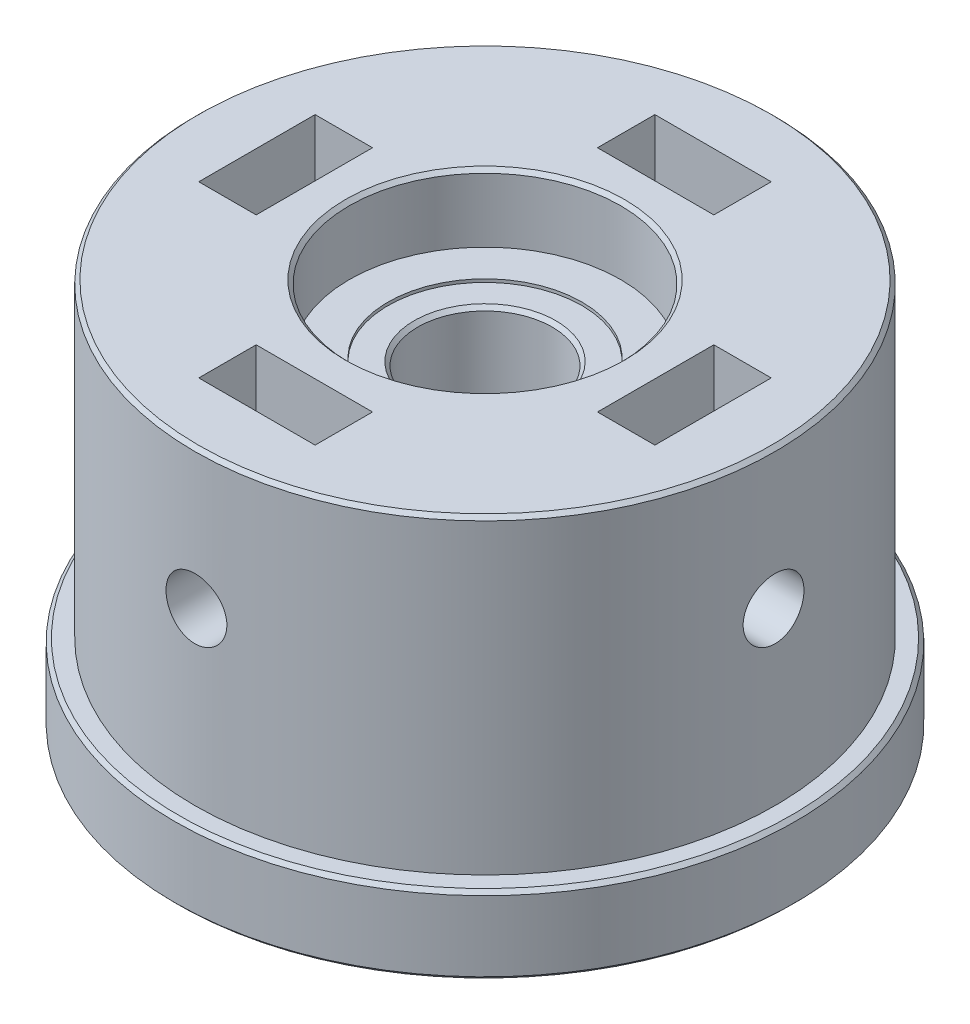
SolidWorks part; units mm, degrees
material "Nylon 101"
ref_plane "Front Plane" through (0, 0, 0) normal (0, 0, 1) x (1, 0, 0)
ref_plane "Top Plane" through (0, 0, 0) normal (0, 1, 0) x (1, 0, 0)
ref_plane "Right Plane" through (0, 0, 0) normal (1, 0, 0) x (0, 0, -1)
sketch "Sketch1" plane through (0, 0, 0) normal (0, 1, 0) x (1, 0, 0)
  circle A0 centre (0, 0) radius 23.749
  dimension "D1" = 47.498
extrude "Boss-Extrude1" add sketch "Sketch1" along normal blind 25.4
sketch "Sketch2" plane through (0, 0, 0) normal (0, -1, 0) x (1, 0, 0)
  circle A0 centre (0, 0) radius 25.4
  dimension "D1" = 50.8
extrude "Boss-Extrude2" add sketch "Sketch2" along normal blind 6.35
sketch "Sketch3" plane through (0, -6.35, 0) normal (0, -1, 0) x (1, 0, 0)
  circle A0 centre (0, 0) radius 5.5
  dimension "D1" = 11
extrude "Cut-Extrude1" cut sketch "Sketch3" against normal through all
sketch "Sketch4" plane through (0, -6.35, 0) normal (0, -1, 0) x (1, 0, 0)
  circle A0 centre (0, 0) radius 11.1125
  dimension "D1" = 22.225
extrude "Cut-Extrude2" cut sketch "Sketch4" against normal blind 5.5372
sketch "Sketch5" plane through (0, -0.8128, 0) normal (0, -1, 0) x (1, 0, 0)
  circle A0 centre (0, 0) radius 7.9375
  dimension "D1" = 15.875
extrude "Cut-Extrude3" cut sketch "Sketch5" against normal blind 0.254
ref_plane "Plane1" through (0, 9.525, 0) normal (0, 1, 0) x (1, 0, 0)
mirror "Mirror1" about plane through (0, 9.525, 0) normal (0, 1, 0) of "Cut-Extrude2", "Cut-Extrude3"
chamfer "Chamfer1" distance 0.3 angle 45 7 edges at (0, 0, -25.4) (0, -6.35, -25.4) (0, -6.35, -11.1125) (0, 25.4, 23.749) (0, 19.6088, 5.5) (0, -0.5588, -5.5) (0, 25.4, -11.1125)
sketch "Sketch6" plane through (0, 0, 0) normal (0, 0, 1) x (1, 0, 0)
  line L1 (23.449, 25.4) -> (-23.449, 25.4) construction
  circle A0 centre (0, 13.97) radius 2.4892
  point P2 (0, 0)
  dimension "D1" = 4.9784
  dimension "D2" = 11.43
sketch "Sketch7" plane through (0, 0, 0) normal (1, 0, 0) x (0, 0, -1)
  line L0 (0, 16.4592) -> (0, 11.4808) construction
  circle A0 centre (0, 13.97) radius 2.4892
  point P4 (0, 6.35)
  dimension "D1" = 4.9784
sketch "Sketch8" plane through (0, 25.4, 0) normal (0, 1, 0) x (1, 0, 0)
  line L0 (18.669, 4.7625) -> (18.669, -4.7625)
  line L1 (-4.7625, 13.97) -> (4.7625, 13.97)
  line L2 (-4.7625, 13.97) -> (-4.7625, 18.669)
  line L3 (-4.7625, 18.669) -> (4.7625, 18.669)
  line L4 (4.7625, 13.97) -> (4.7625, 18.669)
  line L5 (-4.7625, 13.97) -> (4.7625, 18.669) construction
  line L6 (-4.7625, 18.669) -> (4.7625, 13.97) construction
  line L7 (13.97, 4.7625) -> (18.669, 4.7625)
  line L8 (13.97, 4.7625) -> (13.97, -4.7625)
  line L9 (13.97, -4.7625) -> (18.669, -4.7625)
  line L10 (4.7625, -18.669) -> (-4.7625, -18.669)
  line L11 (4.7625, -13.97) -> (4.7625, -18.669)
  line L12 (4.7625, -13.97) -> (-4.7625, -13.97)
  line L13 (-4.7625, -13.97) -> (-4.7625, -18.669)
  line L14 (-18.669, -4.7625) -> (-18.669, 4.7625)
  line L15 (-13.97, -4.7625) -> (-18.669, -4.7625)
  line L16 (-13.97, -4.7625) -> (-13.97, 4.7625)
  line L17 (-13.97, 4.7625) -> (-18.669, 4.7625)
  point P0 (0, 16.3195)
  point P5 (0, 0)
  point P21 (0, 0)
  dimension "D1" = 4.699
  dimension "D2" = 9.525
  dimension "D3" = 13.97
  dimension "D4" = 4
extrude "Cut-Extrude4" cut sketch "Sketch8" against normal blind 16.1925
ref_plane "Plane2" through (0, 0, 25.4) normal (0, 0, 1) x (1, 0, 0)
sketch "Sketch9" plane through (0, 0, 25.4) normal (0, 0, 1) x (1, 0, 0)
  circle A0 centre (0, 13.97) radius 2.4892 construction
  circle A1 centre (0, 13.97) radius 2.4892
extrude "Cut-Extrude5" cut sketch "Sketch9" against normal blind 7.62
ref_plane "Plane3" through (25.4, 0, 0) normal (1, 0, 0) x (0, 0, -1)
sketch "Sketch10" plane through (25.4, 0, 0) normal (1, 0, 0) x (0, 0, -1)
  circle A0 centre (0, 13.97) radius 2.4892 construction
  circle A1 centre (0, 13.97) radius 2.4892
extrude "Cut-Extrude6" cut sketch "Sketch10" against normal blind 7.62
mirror "Mirror2" about plane through (0, 0, 0) normal (0, 0, 1) of "Cut-Extrude5"
mirror "Mirror3" about plane through (0, 0, 0) normal (1, 0, 0) of "Cut-Extrude6"
equation "\"D1@Chamfer1\"=.3mm"
